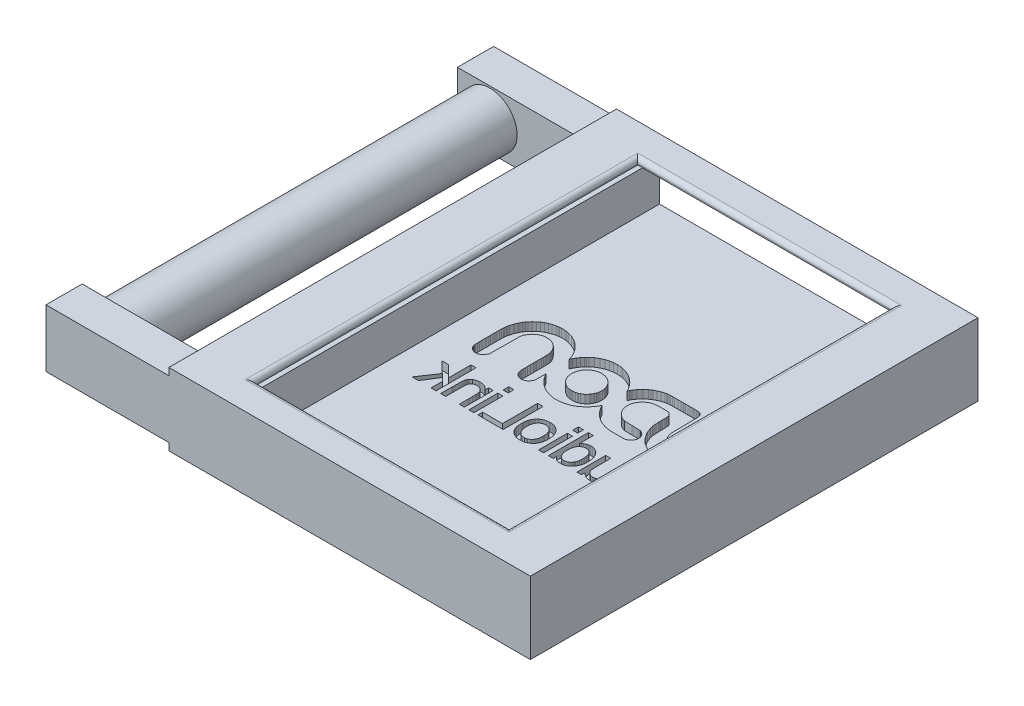
SolidWorks part; units mm, degrees
material "6061 Alloy"
ref_plane "Front" through (0, 0, 0) normal (0, 0, 1) x (1, 0, 0)
ref_plane "Top" through (0, 0, 0) normal (0, 1, 0) x (1, 0, 0)
ref_plane "Right" through (0, 0, 0) normal (1, 0, 0) x (0, 0, -1)
sketch "Sketch1" plane through (0, 0, 0) normal (0, 1, 0) x (1, 0, 0)
  line L1 (-100, -123.825) -> (100, -123.825)
  line L2 (-100, -123.825) -> (-100, 123.825)
  line L3 (-100, 123.825) -> (100, 123.825)
  line L4 (100, -123.825) -> (100, 123.825)
  line L5 (-100, -123.825) -> (100, 123.825) construction
  line L6 (-100, 123.825) -> (100, -123.825) construction
  point P0 (0, 0)
  dimension "D1" = 247.65
  dimension "D2" = 200
extrude "Boss-Extrude1" add sketch "Sketch1" along normal mid plane 40
sketch "Sketch2" plane through (0, 0, 0) normal (0, 1, 0) x (1, 0, 0)
  line L1 (-100, 123.825) -> (-168, 123.825)
  line L2 (-100, 123.825) -> (-100, 103.825)
  line L3 (-100, 103.825) -> (-168, 103.825)
  line L4 (-168, 123.825) -> (-168, 103.825)
  dimension "D1" = 68
  dimension "D2" = 20
extrude "Boss-Extrude2" add sketch "Sketch2" along normal mid plane 32
sketch "Sketch3" plane through (0, 0, 0) normal (0, 0, 1) x (1, 0, 0)
  circle A0 centre (-150, 0) radius 15
  dimension "D1" = 30
  dimension "D2" = 150
extrude "Boss-Extrude3" add sketch "Sketch3" against normal up to surface (103.825 mm away) up to face at (-134, 0, -103.825)
mirror "Mirror1" about plane through (0, 0, 0) normal (0, 0, 1) of "Boss-Extrude2", "Boss-Extrude3"
sketch "Sketch4" plane through (0, 20, 0) normal (0, 1, 0) x (1, 0, 0)
  line L1 (-70.485, -106.045) -> (70.485, -106.045)
  line L2 (-70.485, -106.045) -> (-70.485, 106.045)
  line L3 (-70.485, 106.045) -> (70.485, 106.045)
  line L4 (70.485, -106.045) -> (70.485, 106.045)
  line L5 (-70.485, -106.045) -> (70.485, 106.045) construction
  line L6 (-70.485, 106.045) -> (70.485, -106.045) construction
  point P0 (0, 0)
  dimension "D1" = 212.09
  dimension "D2" = 140.97
extrude "Cut-Extrude1" cut sketch "Sketch4" against normal blind 6.35
sketch "Sketch5" plane through (0, 0, 123.825) normal (0, 0, 1) x (1, 0, 0)
  line L0 (70.485, 13.65) -> (70.485, 20) construction
  line L1 (-87.249, 16.825) -> (87.249, 16.825)
  line L2 (-87.249, 16.825) -> (-87.249, 8.443)
  line L3 (-87.249, 8.443) -> (87.249, 8.443)
  line L4 (87.249, 16.825) -> (87.249, 8.443)
  line L5 (-87.249, 16.825) -> (87.249, 8.443) construction
  line L6 (-87.249, 8.443) -> (87.249, 16.825) construction
  line L7 (-70.485, 13.65) -> (-70.485, 20) construction
  line L8 (70.485, 13.65) -> (70.485, 20) construction
  line L9 (-70.485, 13.65) -> (-70.485, 20) construction
  line L10 (-100, 20) -> (100, 20) construction
  point P0 (0, 12.634)
  dimension "D1" = 8.382
  dimension "D2" = 3.175
  dimension "D3" = 16.764
  dimension "D4" = 16.764
extrude "Cut-Extrude2" cut sketch "Sketch5" along normal offset from surface (246.634 mm away) 16.764 from surface up to face at (0, 16.825, 106.045) offset beyond the face yes starting at face at (-67, 0, -123.825)
fillet "Fillet1" radius 2.54 4 edges at (0, 20, 106.045) (70.485, 20, 0) (-70.485, 20, 0) (0, 20, -106.045)
sketch "Sketch6" plane through (0, 0, -123.825) normal (0, 0, -1) x (-1, 0, 0)
  line L0 (87.249, 8.443) -> (-87.249, 8.443) construction
  line L1 (-76.2, -13.65) -> (76.2, -13.65)
  line L2 (-76.2, -13.65) -> (-76.2, 8.443)
  line L3 (-76.2, 8.443) -> (76.2, 8.443)
  line L4 (76.2, -13.65) -> (76.2, 8.443)
  line L5 (-76.2, -13.65) -> (76.2, 8.443) construction
  line L6 (-76.2, 8.443) -> (76.2, -13.65) construction
  line L7 (-100, -20) -> (100, -20) construction
  point P0 (0, -2.6035)
  dimension "D1" = 152.4
  dimension "D2" = 6.35
extrude "Cut-Extrude3" cut sketch "Sketch6" against normal up to surface (246.634 mm away) up to face at (0, 12.634, 122.809)
sketch "Sketch9" plane through (0, -20, 0) normal (0, -1, 0) x (1, 0, 0)
  line L0 (47.93, -1.8124) -> (48.8593, -2.019)
  line L1 (48.8593, -2.019) -> (50.5205, -2.4998)
  line L2 (50.5205, -2.4998) -> (52.0185, -3.112)
  line L3 (52.0185, -3.112) -> (53.4733, -3.9044)
  line L4 (53.4733, -3.9044) -> (54.222, -4.3835)
  line L5 (54.222, -4.3835) -> (54.8334, -4.8153)
  line L6 (54.8334, -4.8153) -> (56.0096, -5.784)
  line L7 (56.0096, -5.784) -> (57.1117, -6.8762)
  line L8 (57.1117, -6.8762) -> (58.1253, -8.0714)
  line L9 (58.1253, -8.0714) -> (59.0359, -9.3494)
  line L10 (59.0359, -9.3494) -> (59.829, -10.6898)
  line L11 (59.829, -10.6898) -> (60.49, -12.0723)
  line L12 (60.49, -12.0723) -> (61.0045, -13.4765)
  line L13 (61.0045, -13.4765) -> (61.2023, -14.1804)
  line L14 (61.2023, -14.1804) -> (61.4, -15.0085)
  line L15 (61.4, -15.0085) -> (61.6145, -16.1928)
  line L16 (61.6145, -16.1928) -> (61.7109, -17.0783)
  line L17 (61.7109, -17.0783) -> (61.7768, -18.1482)
  line L18 (61.7768, -18.1482) -> (61.8178, -19.4948)
  line L19 (61.8178, -19.4948) -> (61.8396, -21.2101)
  line L20 (61.8396, -21.2101) -> (61.8467, -22.7941)
  line L21 (61.8467, -22.7941) -> (61.8484, -24.0134)
  line L22 (61.8484, -24.0134) -> (61.8486, -24.6763)
  line L23 (61.8486, -24.6763) -> (61.8486, -25.2604)
  line L24 (61.8486, -25.2604) -> (61.8482, -26.327)
  line L25 (61.8482, -26.327) -> (61.846, -27.691)
  line L26 (61.846, -27.691) -> (61.8385, -29.1187)
  line L27 (61.8385, -29.1187) -> (61.8233, -30.1692)
  line L28 (61.8233, -30.1692) -> (61.798, -30.9181)
  line L29 (61.798, -30.9181) -> (61.7599, -31.4412)
  line L30 (61.7599, -31.4412) -> (61.6732, -31.9679)
  line L31 (61.6732, -31.9679) -> (61.5921, -32.2575)
  line L32 (61.5921, -32.2575) -> (61.4441, -32.651)
  line L33 (61.4441, -32.651) -> (61.0089, -33.4052)
  line L34 (61.0089, -33.4052) -> (60.4202, -34.0791)
  line L35 (60.4202, -34.0791) -> (59.7166, -34.6283)
  line L36 (59.7166, -34.6283) -> (59.3337, -34.8425)
  line L37 (59.3337, -34.8425) -> (58.9346, -35.0064)
  line L38 (58.9346, -35.0064) -> (58.0614, -35.1964)
  line L39 (58.0614, -35.1964) -> (57.1488, -35.2022)
  line L40 (57.1488, -35.2022) -> (56.2694, -35.0232)
  line L41 (56.2694, -35.0232) -> (55.8648, -34.8643)
  line L42 (55.8648, -34.8643) -> (55.3692, -34.5995)
  line L43 (55.3692, -34.5995) -> (54.5302, -33.9483)
  line L44 (54.5302, -33.9483) -> (53.8984, -33.1408)
  line L45 (53.8984, -33.1408) -> (53.4792, -32.1837)
  line L46 (53.4792, -32.1837) -> (53.351, -31.6514)
  line L47 (53.351, -31.6514) -> (53.3349, -31.5347)
  line L48 (53.3349, -31.5347) -> (53.3054, -31.1451)
  line L49 (53.3054, -31.1451) -> (53.2796, -30.5535)
  line L50 (53.2796, -30.5535) -> (53.2577, -29.7676)
  line L51 (53.2577, -29.7676) -> (53.2397, -28.795)
  line L52 (53.2397, -28.795) -> (53.2258, -27.6434)
  line L53 (53.2258, -27.6434) -> (53.2161, -26.3204)
  line L54 (53.2161, -26.3204) -> (53.2108, -24.8337)
  line L55 (53.2108, -24.8337) -> (53.2099, -24.0314)
  line L56 (53.2099, -24.0314) -> (53.2069, -22.5476)
  line L57 (53.2069, -22.5476) -> (53.1942, -20.5567)
  line L58 (53.1942, -20.5567) -> (53.1807, -19.4123)
  line L59 (53.1807, -19.4123) -> (53.1636, -18.4351)
  line L60 (53.1636, -18.4351) -> (53.1432, -17.6434)
  line L61 (53.1432, -17.6434) -> (53.1198, -17.055)
  line L62 (53.1198, -17.055) -> (53.0937, -16.6882)
  line L63 (53.0937, -16.6882) -> (53.0797, -16.5934)
  line L64 (53.0797, -16.5934) -> (52.8926, -15.8966)
  line L65 (52.8926, -15.8966) -> (52.3521, -14.5891)
  line L66 (52.3521, -14.5891) -> (51.6095, -13.4123)
  line L67 (51.6095, -13.4123) -> (50.6885, -12.385)
  line L68 (50.6885, -12.385) -> (49.6127, -11.5261)
  line L69 (49.6127, -11.5261) -> (48.4057, -10.8544)
  line L70 (48.4057, -10.8544) -> (47.0912, -10.3889)
  line L71 (47.0912, -10.3889) -> (45.6927, -10.1483)
  line L72 (45.6927, -10.1483) -> (44.9694, -10.1183)
  line L73 (44.9694, -10.1183) -> (43.9951, -10.1684)
  line L74 (43.9951, -10.1684) -> (42.185, -10.5837)
  line L75 (42.185, -10.5837) -> (41.2769, -10.9654)
  line L76 (41.2769, -10.9654) -> (40.8053, -11.229)
  line L77 (40.8053, -11.229) -> (39.795, -11.9878)
  line L78 (39.795, -11.9878) -> (38.8185, -12.936)
  line L79 (38.8185, -12.936) -> (38.0234, -13.93)
  line L80 (38.0234, -13.93) -> (37.7401, -14.3995)
  line L81 (37.7401, -14.3995) -> (37.5607, -14.7386)
  line L82 (37.5607, -14.7386) -> (37.2712, -15.3057)
  line L83 (37.2712, -15.3057) -> (37.0622, -15.844)
  line L84 (37.0622, -15.844) -> (36.9192, -16.4977)
  line L85 (36.9192, -16.4977) -> (36.8279, -17.4103)
  line L86 (36.8279, -17.4103) -> (36.7846, -18.3514)
  line L87 (36.7846, -18.3514) -> (36.7643, -19.1346)
  line L88 (36.7643, -19.1346) -> (36.7489, -20.0635)
  line L89 (36.7489, -20.0635) -> (36.7365, -21.1561)
  line L90 (36.7365, -21.1561) -> (36.7253, -22.4303)
  line L91 (36.7253, -22.4303) -> (36.7135, -23.9041)
  line L92 (36.7135, -23.9041) -> (36.7068, -24.7214)
  line L93 (36.7068, -24.7214) -> (36.7002, -25.5284)
  line L94 (36.7002, -25.5284) -> (36.6881, -26.9863)
  line L95 (36.6881, -26.9863) -> (36.6766, -28.2491)
  line L96 (36.6766, -28.2491) -> (36.664, -29.3326)
  line L97 (36.664, -29.3326) -> (36.6488, -30.2526)
  line L98 (36.6488, -30.2526) -> (36.6297, -31.0248)
  line L99 (36.6297, -31.0248) -> (36.5902, -31.9403)
  line L100 (36.5902, -31.9403) -> (36.5095, -32.7906)
  line L101 (36.5095, -32.7906) -> (36.3858, -33.3329)
  line L102 (36.3858, -33.3329) -> (36.0936, -33.8445)
  line L103 (36.0936, -33.8445) -> (35.8102, -34.1679)
  line L104 (35.8102, -34.1679) -> (35.3632, -34.5848)
  line L105 (35.3632, -34.5848) -> (34.8735, -34.9207)
  line L106 (34.8735, -34.9207) -> (34.6857, -35.0125)
  line L107 (34.6857, -35.0125) -> (34.2701, -35.1085)
  line L108 (34.2701, -35.1085) -> (33.7539, -35.1494)
  line L109 (33.7539, -35.1494) -> (32.9267, -35.1756)
  line L110 (32.9267, -35.1756) -> (32.0403, -35.1876)
  line L111 (32.0403, -35.1876) -> (31.2987, -35.1927)
  line L112 (31.2987, -35.1927) -> (30.4215, -35.196)
  line L113 (30.4215, -35.196) -> (29.3959, -35.1979)
  line L114 (29.3959, -35.1979) -> (28.2091, -35.1987)
  line L115 (28.2091, -35.1987) -> (26.8482, -35.1989)
  line L116 (26.8482, -35.1989) -> (26.0985, -35.1989)
  line L117 (26.0985, -35.1989) -> (25.4237, -35.1989)
  line L118 (25.4237, -35.1989) -> (24.1823, -35.1982)
  line L119 (24.1823, -35.1982) -> (22.573, -35.1954)
  line L120 (22.573, -35.1954) -> (20.8496, -35.1874)
  line L121 (20.8496, -35.1874) -> (19.5398, -35.1726)
  line L122 (19.5398, -35.1726) -> (18.5682, -35.1492)
  line L123 (18.5682, -35.1492) -> (17.8592, -35.1155)
  line L124 (17.8592, -35.1155) -> (17.1232, -35.0417)
  line L125 (17.1232, -35.0417) -> (16.7409, -34.9742)
  line L126 (16.7409, -34.9742) -> (15.8881, -34.7797)
  line L127 (15.8881, -34.7797) -> (14.2327, -34.2776)
  line L128 (14.2327, -34.2776) -> (12.6521, -33.628)
  line L129 (12.6521, -33.628) -> (11.1562, -32.8348)
  line L130 (11.1562, -32.8348) -> (10.443, -32.3856)
  line L131 (10.443, -32.3856) -> (9.6232, -31.7926)
  line L132 (9.6232, -31.7926) -> (8.0064, -30.3585)
  line L133 (8.0064, -30.3585) -> (6.5288, -28.7146)
  line L134 (6.5288, -28.7146) -> (5.3208, -27.006)
  line L135 (5.3208, -27.006) -> (4.8587, -26.1729)
  line L136 (4.8587, -26.1729) -> (4.4117, -25.2748)
  line L137 (4.4117, -25.2748) -> (3.998, -26.0686)
  line L138 (3.998, -26.0686) -> (3.5333, -26.9017)
  line L139 (3.5333, -26.9017) -> (2.4731, -28.475)
  line L140 (2.4731, -28.475) -> (1.2523, -29.914)
  line L141 (1.2523, -29.914) -> (-0.1132, -31.2064)
  line L142 (-0.1132, -31.2064) -> (-1.607, -32.34)
  line L143 (-1.607, -32.34) -> (-3.2132, -33.3026)
  line L144 (-3.2132, -33.3026) -> (-4.9154, -34.0818)
  line L145 (-4.9154, -34.0818) -> (-6.6976, -34.6655)
  line L146 (-6.6976, -34.6655) -> (-7.6137, -34.8801)
  line L147 (-7.6137, -34.8801) -> (-8.6686, -35.0616)
  line L148 (-8.6686, -35.0616) -> (-10.7713, -35.2252)
  line L149 (-10.7713, -35.2252) -> (-12.8491, -35.1279)
  line L150 (-12.8491, -35.1279) -> (-14.8833, -34.7755)
  line L151 (-14.8833, -34.7755) -> (-16.8553, -34.1736)
  line L152 (-16.8553, -34.1736) -> (-18.7463, -33.3279)
  line L153 (-18.7463, -33.3279) -> (-20.5378, -32.2442)
  line L154 (-20.5378, -32.2442) -> (-22.2109, -30.9281)
  line L155 (-22.2109, -30.9281) -> (-22.9973, -30.1847)
  line L156 (-22.9973, -30.1847) -> (-23.5248, -29.6247)
  line L157 (-23.5248, -29.6247) -> (-24.5397, -28.3737)
  line L158 (-24.5397, -28.3737) -> (-25.4499, -27.0237)
  line L159 (-25.4499, -27.0237) -> (-26.1944, -25.6654)
  line L160 (-26.1944, -25.6654) -> (-26.4854, -25.0115)
  line L161 (-26.4854, -25.0115) -> (-26.7632, -24.328)
  line L162 (-26.7632, -24.328) -> (-27.0924, -25.382)
  line L163 (-27.0924, -25.382) -> (-27.4778, -26.465)
  line L164 (-27.4778, -26.465) -> (-28.506, -28.5948)
  line L165 (-28.506, -28.5948) -> (-29.8176, -30.5858)
  line L166 (-29.8176, -30.5858) -> (-31.3414, -32.3296)
  line L167 (-31.3414, -32.3296) -> (-32.1605, -33.075)
  line L168 (-32.1605, -33.075) -> (-33.1539, -33.8619)
  line L169 (-33.1539, -33.8619) -> (-35.1274, -35.1509)
  line L170 (-35.1274, -35.1509) -> (-37.1834, -36.1065)
  line L171 (-37.1834, -36.1065) -> (-39.442, -36.7846)
  line L172 (-39.442, -36.7846) -> (-40.6848, -37.0371)
  line L173 (-40.6848, -37.0371) -> (-41.3523, -37.1437)
  line L174 (-41.3523, -37.1437) -> (-42.5862, -37.2657)
  line L175 (-42.5862, -37.2657) -> (-43.7685, -37.2661)
  line L176 (-43.7685, -37.2661) -> (-44.9993, -37.1451)
  line L177 (-44.9993, -37.1451) -> (-45.6641, -37.0391)
  line L178 (-45.6641, -37.0391) -> (-46.5297, -36.868)
  line L179 (-46.5297, -36.868) -> (-48.1852, -36.4278)
  line L180 (-48.1852, -36.4278) -> (-49.7428, -35.8549)
  line L181 (-49.7428, -35.8549) -> (-51.2063, -35.1471)
  line L182 (-51.2063, -35.1471) -> (-52.5794, -34.302)
  line L183 (-52.5794, -34.302) -> (-53.8658, -33.3174)
  line L184 (-53.8658, -33.3174) -> (-55.0694, -32.1909)
  line L185 (-55.0694, -32.1909) -> (-56.1937, -30.9202)
  line L186 (-56.1937, -30.9202) -> (-56.7274, -30.2301)
  line L187 (-56.7274, -30.2301) -> (-57.2616, -29.4642)
  line L188 (-57.2616, -29.4642) -> (-58.1905, -27.8525)
  line L189 (-58.1905, -27.8525) -> (-58.9425, -26.1127)
  line L190 (-58.9425, -26.1127) -> (-59.5287, -24.2193)
  line L191 (-59.5287, -24.2193) -> (-59.7631, -23.2069)
  line L192 (-59.7631, -23.2069) -> (-59.8639, -22.7055)
  line L193 (-59.8639, -22.7055) -> (-59.9693, -21.9562)
  line L194 (-59.9693, -21.9562) -> (-60.0143, -21.2913)
  line L195 (-60.0143, -21.2913) -> (-60.0433, -20.3602)
  line L196 (-60.0433, -20.3602) -> (-60.0598, -19.0481)
  line L197 (-60.0598, -19.0481) -> (-60.0662, -17.7451)
  line L198 (-60.0662, -17.7451) -> (-60.0684, -16.6976)
  line L199 (-60.0684, -16.6976) -> (-60.0695, -15.4904)
  line L200 (-60.0695, -15.4904) -> (-60.0699, -14.109)
  line L201 (-60.0699, -14.109) -> (-60.07, -13.3486)
  line L202 (-60.07, -13.3486) -> (-60.0679, -11.6508)
  line L203 (-60.0679, -11.6508) -> (-60.057, -9.3283)
  line L204 (-60.057, -9.3283) -> (-60.0452, -7.9785)
  line L205 (-60.0452, -7.9785) -> (-60.0302, -6.8266)
  line L206 (-60.0302, -6.8266) -> (-60.0125, -5.9063)
  line L207 (-60.0125, -5.9063) -> (-59.9926, -5.2512)
  line L208 (-59.9926, -5.2512) -> (-59.9708, -4.8951)
  line L209 (-59.9708, -4.8951) -> (-59.9593, -4.8396)
  line L210 (-59.9593, -4.8396) -> (-59.9043, -4.756)
  line L211 (-59.9043, -4.756) -> (-59.7656, -4.4437)
  line L212 (-59.7656, -4.4437) -> (-59.699, -4.2534)
  line L213 (-59.699, -4.2534) -> (-59.6021, -4.0237)
  line L214 (-59.6021, -4.0237) -> (-59.2623, -3.4944)
  line L215 (-59.2623, -3.4944) -> (-58.5336, -2.6951)
  line L216 (-58.5336, -2.6951) -> (-58.0151, -2.2908)
  line L217 (-58.0151, -2.2908) -> (-57.7273, -2.1311)
  line L218 (-57.7273, -2.1311) -> (-57.055, -1.8689)
  line L219 (-57.055, -1.8689) -> (-56.3263, -1.7002)
  line L220 (-56.3263, -1.7002) -> (-55.6278, -1.6448)
  line L221 (-55.6278, -1.6448) -> (-55.3171, -1.666)
  line L222 (-55.3171, -1.666) -> (-54.7785, -1.7767)
  line L223 (-54.7785, -1.7767) -> (-53.7585, -2.2139)
  line L224 (-53.7585, -2.2139) -> (-52.8596, -2.9046)
  line L225 (-52.8596, -2.9046) -> (-52.136, -3.807)
  line L226 (-52.136, -3.807) -> (-51.8568, -4.3246)
  line L227 (-51.8568, -4.3246) -> (-51.4985, -5.0999)
  line L228 (-51.4985, -5.0999) -> (-51.4312, -13.6724)
  line L229 (-51.4312, -13.6724) -> (-51.4252, -14.4369)
  line L230 (-51.4252, -14.4369) -> (-51.4139, -15.8277)
  line L231 (-51.4139, -15.8277) -> (-51.4034, -17.0448)
  line L232 (-51.4034, -17.0448) -> (-51.393, -18.101)
  line L233 (-51.393, -18.101) -> (-51.3824, -19.0094)
  line L234 (-51.3824, -19.0094) -> (-51.371, -19.7826)
  line L235 (-51.371, -19.7826) -> (-51.3516, -20.7173)
  line L236 (-51.3516, -20.7173) -> (-51.3186, -21.6106)
  line L237 (-51.3186, -21.6106) -> (-51.2741, -22.1949)
  line L238 (-51.2741, -22.1949) -> (-51.1775, -22.7169)
  line L239 (-51.1775, -22.7169) -> (-51.0877, -22.9784)
  line L240 (-51.0877, -22.9784) -> (-50.776, -23.7156)
  line L241 (-50.776, -23.7156) -> (-49.9983, -25.0764)
  line L242 (-49.9983, -25.0764) -> (-49.0459, -26.2477)
  line L243 (-49.0459, -26.2477) -> (-47.9559, -27.1837)
  line L244 (-47.9559, -27.1837) -> (-47.371, -27.5492)
  line L245 (-47.371, -27.5492) -> (-46.8306, -27.8335)
  line L246 (-46.8306, -27.8335) -> (-45.853, -28.2463)
  line L247 (-45.853, -28.2463) -> (-44.8852, -28.4825)
  line L248 (-44.8852, -28.4825) -> (-43.7739, -28.5794)
  line L249 (-43.7739, -28.5794) -> (-43.1165, -28.5874)
  line L250 (-43.1165, -28.5874) -> (-42.6016, -28.5831)
  line L251 (-42.6016, -28.5831) -> (-41.8473, -28.5534)
  line L252 (-41.8473, -28.5534) -> (-41.2968, -28.4714)
  line L253 (-41.2968, -28.4714) -> (-40.7543, -28.3077)
  line L254 (-40.7543, -28.3077) -> (-40.4247, -28.186)
  line L255 (-40.4247, -28.186) -> (-39.9657, -27.9967)
  line L256 (-39.9657, -27.9967) -> (-39.0406, -27.5409)
  line L257 (-39.0406, -27.5409) -> (-38.6885, -27.3306)
  line L258 (-38.6885, -27.3306) -> (-38.2703, -27.0276)
  line L259 (-38.2703, -27.0276) -> (-37.4493, -26.2898)
  line L260 (-37.4493, -26.2898) -> (-36.6972, -25.4315)
  line L261 (-36.6972, -25.4315) -> (-36.0723, -24.5191)
  line L262 (-36.0723, -24.5191) -> (-35.8257, -24.0634)
  line L263 (-35.8257, -24.0634) -> (-35.5228, -23.4356)
  line L264 (-35.5228, -23.4356) -> (-35.2091, -22.5816)
  line L265 (-35.2091, -22.5816) -> (-35.0772, -21.8826)
  line L266 (-35.0772, -21.8826) -> (-34.9942, -20.9297)
  line L267 (-34.9942, -20.9297) -> (-34.9571, -19.9706)
  line L268 (-34.9571, -19.9706) -> (-34.9417, -19.1848)
  line L269 (-34.9417, -19.1848) -> (-34.9322, -18.2629)
  line L270 (-34.9322, -18.2629) -> (-34.9272, -17.1889)
  line L271 (-34.9272, -17.1889) -> (-34.9253, -15.9467)
  line L272 (-34.9253, -15.9467) -> (-34.925, -14.52)
  line L273 (-34.925, -14.52) -> (-34.925, -13.7326)
  line L274 (-34.925, -13.7326) -> (-34.9244, -12.8119)
  line L275 (-34.9244, -12.8119) -> (-34.9199, -11.1176)
  line L276 (-34.9199, -11.1176) -> (-34.911, -9.6236)
  line L277 (-34.911, -9.6236) -> (-34.8978, -8.335)
  line L278 (-34.8978, -8.335) -> (-34.8803, -7.2571)
  line L279 (-34.8803, -7.2571) -> (-34.8587, -6.3951)
  line L280 (-34.8587, -6.3951) -> (-34.833, -5.7541)
  line L281 (-34.833, -5.7541) -> (-34.8033, -5.3394)
  line L282 (-34.8033, -5.3394) -> (-34.787, -5.2185)
  line L283 (-34.787, -5.2185) -> (-34.6999, -4.8323)
  line L284 (-34.6999, -4.8323) -> (-34.4399, -4.1124)
  line L285 (-34.4399, -4.1124) -> (-34.0739, -3.4695)
  line L286 (-34.0739, -3.4695) -> (-33.6116, -2.9118)
  line L287 (-33.6116, -2.9118) -> (-33.063, -2.4477)
  line L288 (-33.063, -2.4477) -> (-32.4378, -2.0856)
  line L289 (-32.4378, -2.0856) -> (-31.746, -1.8338)
  line L290 (-31.746, -1.8338) -> (-30.9973, -1.7005)
  line L291 (-30.9973, -1.7005) -> (-30.6047, -1.681)
  line L292 (-30.6047, -1.681) -> (-29.981, -1.7185)
  line L293 (-29.981, -1.7185) -> (-28.8386, -2.046)
  line L294 (-28.8386, -2.046) -> (-27.851, -2.7004)
  line L295 (-27.851, -2.7004) -> (-27.0358, -3.6702)
  line L296 (-27.0358, -3.6702) -> (-26.6984, -4.2697)
  line L297 (-26.6984, -4.2697) -> (-26.585, -4.5073)
  line L298 (-26.585, -4.5073) -> (-26.4362, -4.9681)
  line L299 (-26.4362, -4.9681) -> (-26.3751, -5.4722)
  line L300 (-26.3751, -5.4722) -> (-26.3502, -5.9652)
  line L301 (-26.3502, -5.9652) -> (-26.3328, -6.6345)
  line L302 (-26.3328, -6.6345) -> (-26.3184, -7.5234)
  line L303 (-26.3184, -7.5234) -> (-26.3109, -8.0637)
  line L304 (-26.3109, -8.0637) -> (-26.2689, -11.1546)
  line L305 (-26.2689, -11.1546) -> (-25.7104, -10.1744)
  line L306 (-25.7104, -10.1744) -> (-25.2365, -9.3917)
  line L307 (-25.2365, -9.3917) -> (-24.177, -7.917)
  line L308 (-24.177, -7.917) -> (-22.9796, -6.5718)
  line L309 (-22.9796, -6.5718) -> (-21.6581, -5.3662)
  line L310 (-21.6581, -5.3662) -> (-20.2262, -4.3101)
  line L311 (-20.2262, -4.3101) -> (-18.6974, -3.4138)
  line L312 (-18.6974, -3.4138) -> (-17.0854, -2.6873)
  line L313 (-17.0854, -2.6873) -> (-15.404, -2.1406)
  line L314 (-15.404, -2.1406) -> (-14.5415, -1.9379)
  line L315 (-14.5415, -1.9379) -> (-14.0986, -1.847)
  line L316 (-14.0986, -1.847) -> (-13.2307, -1.6695)
  line L317 (-13.2307, -1.6695) -> (-12.9126, -1.6047)
  line L318 (-12.9126, -1.6047) -> (-12.466, -1.5337)
  line L319 (-12.466, -1.5337) -> (-11.4389, -1.475)
  line L320 (-11.4389, -1.475) -> (-9.655, -1.5789)
  line L321 (-9.655, -1.5789) -> (-7.0806, -2.0304)
  line L322 (-7.0806, -2.0304) -> (-5.2179, -2.5662)
  line L323 (-5.2179, -2.5662) -> (-4.1006, -3.001)
  line L324 (-4.1006, -3.001) -> (-3.5977, -3.2385)
  line L325 (-3.5977, -3.2385) -> (-2.4454, -3.8854)
  line L326 (-2.4454, -3.8854) -> (-0.2515, -5.484)
  line L327 (-0.2515, -5.484) -> (1.7045, -7.4005)
  line L328 (1.7045, -7.4005) -> (3.3142, -9.5288)
  line L329 (3.3142, -9.5288) -> (3.9552, -10.6392)
  line L330 (3.9552, -10.6392) -> (4.3904, -11.4794)
  line L331 (4.3904, -11.4794) -> (4.9413, -10.4279)
  line L332 (4.9413, -10.4279) -> (5.3263, -9.7401)
  line L333 (5.3263, -9.7401) -> (6.2161, -8.4126)
  line L334 (6.2161, -8.4126) -> (7.2502, -7.1614)
  line L335 (7.2502, -7.1614) -> (8.4106, -6.0016)
  line L336 (8.4106, -6.0016) -> (9.6792, -4.9484)
  line L337 (9.6792, -4.9484) -> (11.0377, -4.0168)
  line L338 (11.0377, -4.0168) -> (12.468, -3.2219)
  line L339 (12.468, -3.2219) -> (13.9519, -2.5787)
  line L340 (13.9519, -2.5787) -> (14.7084, -2.3187)
  line L341 (14.7084, -2.3187) -> (15.5331, -2.0749)
  line L342 (15.5331, -2.0749) -> (17.1024, -1.7339)
  line L343 (17.1024, -1.7339) -> (18.4035, -1.5869)
  line L344 (18.4035, -1.5869) -> (19.4225, -1.5316)
  line L345 (19.4225, -1.5316) -> (20.6203, -1.5047)
  line L346 (20.6203, -1.5047) -> (22.0461, -1.5013)
  line L347 (22.0461, -1.5013) -> (22.86, -1.5068)
  line L348 (22.86, -1.5068) -> (26.9875, -1.5439)
  line L349 (26.9875, -1.5439) -> (27.7793, -1.9096)
  line L350 (27.7793, -1.9096) -> (28.2315, -2.1493)
  line L351 (28.2315, -2.1493) -> (29.0123, -2.7454)
  line L352 (29.0123, -2.7454) -> (29.621, -3.4699)
  line L353 (29.621, -3.4699) -> (30.0487, -4.2897)
  line L354 (30.0487, -4.2897) -> (30.2865, -5.172)
  line L355 (30.2865, -5.172) -> (30.3255, -6.0836)
  line L356 (30.3255, -6.0836) -> (30.1568, -6.9916)
  line L357 (30.1568, -6.9916) -> (29.7716, -7.8632)
  line L358 (29.7716, -7.8632) -> (29.495, -8.2749)
  line L359 (29.495, -8.2749) -> (29.0358, -8.7861)
  line L360 (29.0358, -8.7861) -> (27.8992, -9.6272)
  line L361 (27.8992, -9.6272) -> (27.3275, -9.8789)
  line L362 (27.3275, -9.8789) -> (27.2543, -9.8968)
  line L363 (27.2543, -9.8968) -> (27.0073, -9.9317)
  line L364 (27.0073, -9.9317) -> (26.3933, -9.981)
  line L365 (26.3933, -9.981) -> (25.1434, -10.0404)
  line L366 (25.1434, -10.0404) -> (23.4327, -10.0907)
  line L367 (23.4327, -10.0907) -> (22.4155, -10.1121)
  line L368 (22.4155, -10.1121) -> (17.9705, -10.1949)
  line L369 (17.9705, -10.1949) -> (17.0207, -10.5531)
  line L370 (17.0207, -10.5531) -> (16.3324, -10.846)
  line L371 (16.3324, -10.846) -> (15.0675, -11.5821)
  line L372 (15.0675, -11.5821) -> (13.9649, -12.4963)
  line L373 (13.9649, -12.4963) -> (13.0414, -13.5613)
  line L374 (13.0414, -13.5613) -> (12.3136, -14.7502)
  line L375 (12.3136, -14.7502) -> (11.7978, -16.0359)
  line L376 (11.7978, -16.0359) -> (11.5108, -17.3913)
  line L377 (11.5108, -17.3913) -> (11.4692, -18.7893)
  line L378 (11.4692, -18.7893) -> (11.5455, -19.4959)
  line L379 (11.5455, -19.4959) -> (11.6767, -20.1945)
  line L380 (11.6767, -20.1945) -> (12.0623, -21.4564)
  line L381 (12.0623, -21.4564) -> (12.6362, -22.5846)
  line L382 (12.6362, -22.5846) -> (13.4271, -23.6357)
  line L383 (13.4271, -23.6357) -> (13.9129, -24.1499)
  line L384 (13.9129, -24.1499) -> (14.2939, -24.5126)
  line L385 (14.2939, -24.5126) -> (15.0462, -25.1282)
  line L386 (15.0462, -25.1282) -> (16.2354, -25.8314)
  line L387 (16.2354, -25.8314) -> (17.1352, -26.1956)
  line L388 (17.1352, -26.1956) -> (17.6372, -26.3521)
  line L389 (17.6372, -26.3521) -> (18.7495, -26.5798)
  line L390 (18.7495, -26.5798) -> (20.1313, -26.7051)
  line L391 (20.1313, -26.7051) -> (21.4348, -26.7401)
  line L392 (21.4348, -26.7401) -> (22.4663, -26.7384)
  line L393 (22.4663, -26.7384) -> (23.0378, -26.7308)
  line L394 (23.0378, -26.7308) -> (23.5826, -26.7212)
  line L395 (23.5826, -26.7212) -> (24.4877, -26.6984)
  line L396 (24.4877, -26.6984) -> (25.1826, -26.6629)
  line L397 (25.1826, -26.6629) -> (25.7101, -26.6053)
  line L398 (25.7101, -26.6053) -> (26.2808, -26.4567)
  line L399 (26.2808, -26.4567) -> (26.8544, -26.0928)
  line L400 (26.8544, -26.0928) -> (27.1571, -25.8185)
  line L401 (27.1571, -25.8185) -> (27.4357, -25.5494)
  line L402 (27.4357, -25.5494) -> (27.7976, -24.9893)
  line L403 (27.7976, -24.9893) -> (27.9422, -24.292)
  line L404 (27.9422, -24.292) -> (27.9993, -23.5723)
  line L405 (27.9993, -23.5723) -> (28.0381, -22.5723)
  line L406 (28.0381, -22.5723) -> (28.0698, -21.2265)
  line L407 (28.0698, -21.2265) -> (28.0865, -20.4034)
  line L408 (28.0865, -20.4034) -> (28.0982, -19.8547)
  line L409 (28.0982, -19.8547) -> (28.1231, -18.861)
  line L410 (28.1231, -18.861) -> (28.1652, -17.6148)
  line L411 (28.1652, -17.6148) -> (28.2323, -16.3682)
  line L412 (28.2323, -16.3682) -> (28.3151, -15.5383)
  line L413 (28.3151, -15.5383) -> (28.3635, -15.2599)
  line L414 (28.3635, -15.2599) -> (28.7437, -13.783)
  line L415 (28.7437, -13.783) -> (29.837, -11.001)
  line L416 (29.837, -11.001) -> (31.3485, -8.4905)
  line L417 (31.3485, -8.4905) -> (32.7383, -6.8163)
  line L418 (32.7383, -6.8163) -> (33.7796, -5.8114)
  line L419 (33.7796, -5.8114) -> (34.3332, -5.3448)
  line L420 (34.3332, -5.3448) -> (35.1932, -4.6885)
  line L421 (35.1932, -4.6885) -> (36.9311, -3.5871)
  line L422 (36.9311, -3.5871) -> (38.7596, -2.7366)
  line L423 (38.7596, -2.7366) -> (40.7584, -2.0999)
  line L424 (40.7584, -2.0999) -> (41.8465, -1.85)
  line L425 (41.8465, -1.85) -> (42.6782, -1.6958)
  line L426 (42.6782, -1.6958) -> (44.211, -1.5159)
  line L427 (44.211, -1.5159) -> (45.6624, -1.507)
  line L428 (45.6624, -1.507) -> (47.1435, -1.6682)
  line L429 (47.1435, -1.6682) -> (47.93, -1.8124)
  line L430 (22.479, 27.6239) -> (22.8987, 27.475)
  line L431 (22.8987, 27.475) -> (23.6208, 27.1527)
  line L432 (23.6208, 27.1527) -> (24.2551, 26.7544)
  line L433 (24.2551, 26.7544) -> (24.884, 26.2286)
  line L434 (24.884, 26.2286) -> (25.2222, 25.9016)
  line L435 (25.2222, 25.9016) -> (25.5751, 25.5248)
  line L436 (25.5751, 25.5248) -> (26.1896, 24.7175)
  line L437 (26.1896, 24.7175) -> (26.6918, 23.8219)
  line L438 (26.6918, 23.8219) -> (27.0931, 22.8177)
  line L439 (27.0931, 22.8177) -> (27.2595, 22.2686)
  line L440 (27.2595, 22.2686) -> (27.3162, 22.0251)
  line L441 (27.3162, 22.0251) -> (27.407, 21.4175)
  line L442 (27.407, 21.4175) -> (27.4863, 20.2929)
  line L443 (27.4863, 20.2929) -> (27.4858, 18.6436)
  line L444 (27.4858, 18.6436) -> (27.4058, 17.5012)
  line L445 (27.4058, 17.5012) -> (27.3146, 16.8732)
  line L446 (27.3146, 16.8732) -> (27.2577, 16.6171)
  line L447 (27.2577, 16.6171) -> (27.0032, 15.7815)
  line L448 (27.0032, 15.7815) -> (26.3203, 14.2855)
  line L449 (26.3203, 14.2855) -> (25.4256, 13.0509)
  line L450 (25.4256, 13.0509) -> (24.3438, 12.1115)
  line L451 (24.3438, 12.1115) -> (23.7403, 11.7631)
  line L452 (23.7403, 11.7631) -> (23.3338, 11.5756)
  line L453 (23.3338, 11.5756) -> (22.5586, 11.3014)
  line L454 (22.5586, 11.3014) -> (21.7685, 11.1489)
  line L455 (21.7685, 11.1489) -> (20.8854, 11.1028)
  line L456 (20.8854, 11.1028) -> (20.3844, 11.115)
  line L457 (20.3844, 11.115) -> (20.0415, 11.1329)
  line L458 (20.0415, 11.1329) -> (19.5012, 11.1873)
  line L459 (19.5012, 11.1873) -> (18.8608, 11.3595)
  line L460 (18.8608, 11.3595) -> (18.396, 11.5692)
  line L461 (18.396, 11.5692) -> (17.6424, 12.0268)
  line L462 (17.6424, 12.0268) -> (16.9802, 12.5609)
  line L463 (16.9802, 12.5609) -> (16.383, 13.1497)
  line L464 (16.383, 13.1497) -> (16.383, 9.2636)
  line L465 (16.383, 9.2636) -> (16.383, 5.3776)
  line L466 (16.383, 5.3776) -> (14.986, 5.3776)
  line L467 (14.986, 5.3776) -> (13.589, 5.3776)
  line L468 (13.589, 5.3776) -> (13.589, 16.4266)
  line L469 (13.589, 16.4266) -> (13.589, 27.4756)
  line L470 (13.589, 27.4756) -> (14.9225, 27.4756)
  line L471 (14.9225, 27.4756) -> (16.256, 27.4756)
  line L472 (16.256, 27.4756) -> (16.256, 26.592)
  line L473 (16.256, 26.592) -> (16.256, 25.7085)
  line L474 (16.256, 25.7085) -> (16.8459, 26.3391)
  line L475 (16.8459, 26.3391) -> (17.1471, 26.6263)
  line L476 (17.1471, 26.6263) -> (17.8866, 27.1671)
  line L477 (17.8866, 27.1671) -> (18.2698, 27.3803)
  line L478 (18.2698, 27.3803) -> (18.7579, 27.6029)
  line L479 (18.7579, 27.6029) -> (19.4199, 27.7687)
  line L480 (19.4199, 27.7687) -> (20.0305, 27.8114)
  line L481 (20.0305, 27.8114) -> (20.4421, 27.8237)
  line L482 (20.4421, 27.8237) -> (20.8023, 27.8296)
  line L483 (20.8023, 27.8296) -> (21.3963, 27.8185)
  line L484 (21.3963, 27.8185) -> (22.0791, 27.7338)
  line L485 (22.0791, 27.7338) -> (22.479, 27.6239)
  line L486 (0.2993, 27.6553) -> (1.0056, 27.441)
  line L487 (1.0056, 27.441) -> (2.3336, 26.7855)
  line L488 (2.3336, 26.7855) -> (3.4968, 25.8685)
  line L489 (3.4968, 25.8685) -> (4.4331, 24.7391)
  line L490 (4.4331, 24.7391) -> (4.7966, 24.1101)
  line L491 (4.7966, 24.1101) -> (5.0057, 23.6647)
  line L492 (5.0057, 23.6647) -> (5.3258, 22.7767)
  line L493 (5.3258, 22.7767) -> (5.5336, 21.806)
  line L494 (5.5336, 21.806) -> (5.6512, 20.6494)
  line L495 (5.6512, 20.6494) -> (5.683, 19.9691)
  line L496 (5.683, 19.9691) -> (5.6979, 19.1586)
  line L497 (5.6979, 19.1586) -> (5.6354, 17.7727)
  line L498 (5.6354, 17.7727) -> (5.4312, 16.5926)
  line L499 (5.4312, 16.5926) -> (5.0632, 15.4892)
  line L500 (5.0632, 15.4892) -> (4.8107, 14.9259)
  line L501 (4.8107, 14.9259) -> (4.5421, 14.4178)
  line L502 (4.5421, 14.4178) -> (3.9128, 13.5164)
  line L503 (3.9128, 13.5164) -> (3.1506, 12.7581)
  line L504 (3.1506, 12.7581) -> (2.2435, 12.1308)
  line L505 (2.2435, 12.1308) -> (1.7317, 11.8626)
  line L506 (1.7317, 11.8626) -> (1.2778, 11.656)
  line L507 (1.2778, 11.656) -> (0.4519, 11.3533)
  line L508 (0.4519, 11.3533) -> (-0.3621, 11.1771)
  line L509 (-0.3621, 11.1771) -> (-1.2809, 11.102)
  line L510 (-1.2809, 11.102) -> (-1.816, 11.0944)
  line L511 (-1.816, 11.0944) -> (-2.4479, 11.1159)
  line L512 (-2.4479, 11.1159) -> (-3.6445, 11.2798)
  line L513 (-3.6445, 11.2798) -> (-4.7465, 11.6015)
  line L514 (-4.7465, 11.6015) -> (-5.7479, 12.0769)
  line L515 (-5.7479, 12.0769) -> (-6.6427, 12.7016)
  line L516 (-6.6427, 12.7016) -> (-7.4249, 13.4715)
  line L517 (-7.4249, 13.4715) -> (-8.0885, 14.3824)
  line L518 (-8.0885, 14.3824) -> (-8.6273, 15.4301)
  line L519 (-8.6273, 15.4301) -> (-8.8481, 16.0039)
  line L520 (-8.8481, 16.0039) -> (-9.0313, 16.5932)
  line L521 (-9.0313, 16.5932) -> (-9.1787, 17.5052)
  line L522 (-9.1787, 17.5052) -> (-9.2267, 18.3941)
  line L523 (-9.2267, 18.3941) -> (-9.2446, 18.9903)
  line L524 (-9.2446, 18.9903) -> (-9.2554, 19.8309)
  line L525 (-9.2554, 19.8309) -> (-9.1924, 21.2543)
  line L526 (-9.1924, 21.2543) -> (-9.0002, 22.4368)
  line L527 (-9.0002, 22.4368) -> (-8.6586, 23.5017)
  line L528 (-8.6586, 23.5017) -> (-8.4256, 24.0285)
  line L529 (-8.4256, 24.0285) -> (-8.0707, 24.6639)
  line L530 (-8.0707, 24.6639) -> (-7.1311, 25.8054)
  line L531 (-7.1311, 25.8054) -> (-5.9292, 26.7403)
  line L532 (-5.9292, 26.7403) -> (-4.5186, 27.4269)
  line L533 (-4.5186, 27.4269) -> (-3.7516, 27.6642)
  line L534 (-3.7516, 27.6642) -> (-3.3479, 27.7427)
  line L535 (-3.3479, 27.7427) -> (-2.321, 27.8312)
  line L536 (-2.321, 27.8312) -> (-1.1768, 27.8287)
  line L537 (-1.1768, 27.8287) -> (-0.1256, 27.7357)
  line L538 (-0.1256, 27.7357) -> (0.2993, 27.6553)
  line L539 (63.5569, 26.3643) -> (63.4932, 26.1997)
  line L540 (63.4932, 26.1997) -> (63.2571, 25.5875)
  line L541 (63.2571, 25.5875) -> (62.8908, 24.6356)
  line L542 (62.8908, 24.6356) -> (62.4116, 23.3892)
  line L543 (62.4116, 23.3892) -> (61.8368, 21.8934)
  line L544 (61.8368, 21.8934) -> (61.1838, 20.1935)
  line L545 (61.1838, 20.1935) -> (60.0957, 17.3597)
  line L546 (60.0957, 17.3597) -> (59.3232, 15.3471)
  line L547 (59.3232, 15.3471) -> (55.5217, 5.4411)
  line L548 (55.5217, 5.4411) -> (53.8743, 5.4057)
  line L549 (53.8743, 5.4057) -> (53.4453, 5.3985)
  line L550 (53.4453, 5.3985) -> (52.7982, 5.4018)
  line L551 (52.7982, 5.4018) -> (52.3968, 5.4316)
  line L552 (52.3968, 5.4316) -> (52.198, 5.491)
  line L553 (52.198, 5.491) -> (52.1612, 5.5327)
  line L554 (52.1612, 5.5327) -> (52.1124, 5.6527)
  line L555 (52.1124, 5.6527) -> (51.8841, 6.2124)
  line L556 (51.8841, 6.2124) -> (51.5015, 7.1497)
  line L557 (51.5015, 7.1497) -> (50.9886, 8.4057)
  line L558 (50.9886, 8.4057) -> (50.3694, 9.9219)
  line L559 (50.3694, 9.9219) -> (49.6678, 11.6395)
  line L560 (49.6678, 11.6395) -> (48.5134, 14.4652)
  line L561 (48.5134, 14.4652) -> (46.91, 18.3897)
  line L562 (46.91, 18.3897) -> (45.7641, 21.1941)
  line L563 (45.7641, 21.1941) -> (45.0721, 22.8873)
  line L564 (45.0721, 22.8873) -> (44.4657, 24.371)
  line L565 (44.4657, 24.371) -> (43.9688, 25.5865)
  line L566 (43.9688, 25.5865) -> (43.6054, 26.475)
  line L567 (43.6054, 26.475) -> (43.3995, 26.9779)
  line L568 (43.3995, 26.9779) -> (43.3632, 27.0664)
  line L569 (43.3632, 27.0664) -> (43.19, 27.4827)
  line L570 (43.19, 27.4827) -> (44.9249, 27.4474)
  line L571 (44.9249, 27.4474) -> (46.6599, 27.4121)
  line L572 (46.6599, 27.4121) -> (47.9301, 24.0768)
  line L573 (47.9301, 24.0768) -> (49.2004, 20.7415)
  line L574 (49.2004, 20.7415) -> (53.7784, 20.7748)
  line L575 (53.7784, 20.7748) -> (58.3565, 20.8081)
  line L576 (58.3565, 20.8081) -> (59.563, 24.1414)
  line L577 (59.563, 24.1414) -> (60.7695, 27.4747)
  line L578 (60.7695, 27.4747) -> (62.3793, 27.4752)
  line L579 (62.3793, 27.4752) -> (63.9891, 27.4756)
  line L580 (63.9891, 27.4756) -> (63.5569, 26.3643)
  line L581 (-48.514, 16.4266) -> (-48.514, 5.3776)
  line L582 (-48.514, 5.3776) -> (-49.911, 5.3776)
  line L583 (-49.911, 5.3776) -> (-51.308, 5.3776)
  line L584 (-51.308, 5.3776) -> (-51.308, 11.6192)
  line L585 (-51.308, 11.6192) -> (-51.308, 17.8608)
  line L586 (-51.308, 17.8608) -> (-54.4314, 14.6672)
  line L587 (-54.4314, 14.6672) -> (-57.5549, 11.4736)
  line L588 (-57.5549, 11.4736) -> (-59.4162, 11.4765)
  line L589 (-59.4162, 11.4765) -> (-61.2775, 11.4795)
  line L590 (-61.2775, 11.4795) -> (-60.6425, 12.0714)
  line L591 (-60.6425, 12.0714) -> (-60.4652, 12.2392)
  line L592 (-60.4652, 12.2392) -> (-59.8707, 12.8119)
  line L593 (-59.8707, 12.8119) -> (-58.5678, 14.0804)
  line L594 (-58.5678, 14.0804) -> (-57.5721, 15.0561)
  line L595 (-57.5721, 15.0561) -> (-55.1367, 17.4489)
  line L596 (-55.1367, 17.4489) -> (-58.4992, 22.4622)
  line L597 (-58.4992, 22.4622) -> (-61.8616, 27.4756)
  line L598 (-61.8616, 27.4756) -> (-60.1091, 27.4712)
  line L599 (-60.1091, 27.4712) -> (-58.3565, 27.4668)
  line L600 (-58.3565, 27.4668) -> (-55.753, 23.4139)
  line L601 (-55.753, 23.4139) -> (-53.1495, 19.3611)
  line L602 (-53.1495, 19.3611) -> (-52.2288, 20.2719)
  line L603 (-52.2288, 20.2719) -> (-51.308, 21.1827)
  line L604 (-51.308, 21.1827) -> (-51.308, 24.3291)
  line L605 (-51.308, 24.3291) -> (-51.308, 27.4756)
  line L606 (-51.308, 27.4756) -> (-49.911, 27.4756)
  line L607 (-49.911, 27.4756) -> (-48.514, 27.4756)
  line L608 (-48.514, 27.4756) -> (-48.514, 16.4266)
  line L609 (-32.893, 19.4746) -> (-32.893, 11.4736)
  line L610 (-32.893, 11.4736) -> (-34.163, 11.4736)
  line L611 (-34.163, 11.4736) -> (-35.433, 11.4736)
  line L612 (-35.433, 11.4736) -> (-35.433, 12.4454)
  line L613 (-35.433, 12.4454) -> (-35.433, 13.4172)
  line L614 (-35.433, 13.4172) -> (-36.1689, 12.7153)
  line L615 (-36.1689, 12.7153) -> (-36.6616, 12.2805)
  line L616 (-36.6616, 12.2805) -> (-37.6571, 11.6332)
  line L617 (-37.6571, 11.6332) -> (-38.7441, 11.255)
  line L618 (-38.7441, 11.255) -> (-40.0161, 11.1136)
  line L619 (-40.0161, 11.1136) -> (-40.7508, 11.1214)
  line L620 (-40.7508, 11.1214) -> (-41.4958, 11.1796)
  line L621 (-41.4958, 11.1796) -> (-42.7889, 11.4567)
  line L622 (-42.7889, 11.4567) -> (-43.8449, 11.9604)
  line L623 (-43.8449, 11.9604) -> (-44.6948, 12.7055)
  line L624 (-44.6948, 12.7055) -> (-45.0521, 13.1731)
  line L625 (-45.0521, 13.1731) -> (-45.3274, 13.5967)
  line L626 (-45.3274, 13.5967) -> (-45.6172, 14.2253)
  line L627 (-45.6172, 14.2253) -> (-45.7432, 14.777)
  line L628 (-45.7432, 14.777) -> (-45.8275, 15.5443)
  line L629 (-45.8275, 15.5443) -> (-45.8805, 16.6212)
  line L630 (-45.8805, 16.6212) -> (-45.9125, 18.1016)
  line L631 (-45.9125, 18.1016) -> (-45.9289, 19.5332)
  line L632 (-45.9289, 19.5332) -> (-45.9387, 20.6627)
  line L633 (-45.9387, 20.6627) -> (-45.9437, 21.2843)
  line L634 (-45.9437, 21.2843) -> (-45.9931, 27.4756)
  line L635 (-45.9931, 27.4756) -> (-44.5865, 27.4756)
  line L636 (-44.5865, 27.4756) -> (-43.18, 27.4756)
  line L637 (-43.18, 27.4756) -> (-43.1761, 22.4273)
  line L638 (-43.1761, 22.4273) -> (-43.1743, 21.4539)
  line L639 (-43.1743, 21.4539) -> (-43.1634, 19.7848)
  line L640 (-43.1634, 19.7848) -> (-43.14, 18.4478)
  line L641 (-43.14, 18.4478) -> (-43.1009, 17.3974)
  line L642 (-43.1009, 17.3974) -> (-43.0427, 16.5876)
  line L643 (-43.0427, 16.5876) -> (-42.9623, 15.9728)
  line L644 (-42.9623, 15.9728) -> (-42.7926, 15.3162)
  line L645 (-42.7926, 15.3162) -> (-42.642, 14.9889)
  line L646 (-42.642, 14.9889) -> (-42.3907, 14.6209)
  line L647 (-42.3907, 14.6209) -> (-41.7199, 14.0549)
  line L648 (-41.7199, 14.0549) -> (-40.8809, 13.7107)
  line L649 (-40.8809, 13.7107) -> (-39.941, 13.5825)
  line L650 (-39.941, 13.5825) -> (-38.9673, 13.6647)
  line L651 (-38.9673, 13.6647) -> (-38.027, 13.9517)
  line L652 (-38.027, 13.9517) -> (-37.1873, 14.4377)
  line L653 (-37.1873, 14.4377) -> (-36.5156, 15.117)
  line L654 (-36.5156, 15.117) -> (-36.2636, 15.5275)
  line L655 (-36.2636, 15.5275) -> (-36.0921, 15.9049)
  line L656 (-36.0921, 15.9049) -> (-35.9033, 16.5522)
  line L657 (-35.9033, 16.5522) -> (-35.8168, 17.117)
  line L658 (-35.8168, 17.117) -> (-35.7564, 17.8518)
  line L659 (-35.7564, 17.8518) -> (-35.7178, 18.8109)
  line L660 (-35.7178, 18.8109) -> (-35.6964, 20.0485)
  line L661 (-35.6964, 20.0485) -> (-35.6879, 21.6189)
  line L662 (-35.6879, 21.6189) -> (-35.687, 22.5459)
  line L663 (-35.687, 22.5459) -> (-35.687, 27.4756)
  line L664 (-35.687, 27.4756) -> (-34.29, 27.4756)
  line L665 (-34.29, 27.4756) -> (-32.893, 27.4756)
  line L666 (-32.893, 27.4756) -> (-32.893, 19.4746)
  line L667 (38.5193, 27.7174) -> (39.0861, 27.5484)
  line L668 (39.0861, 27.5484) -> (40.1394, 27.0304)
  line L669 (40.1394, 27.0304) -> (41.0268, 26.3192)
  line L670 (41.0268, 26.3192) -> (41.6784, 25.4712)
  line L671 (41.6784, 25.4712) -> (41.8937, 25.0134)
  line L672 (41.8937, 25.0134) -> (42.0468, 24.5585)
  line L673 (42.0468, 24.5585) -> (42.216, 23.7887)
  line L674 (42.216, 23.7887) -> (42.2942, 23.1309)
  line L675 (42.2942, 23.1309) -> (42.3492, 22.2884)
  line L676 (42.3492, 22.2884) -> (42.385, 21.2019)
  line L677 (42.385, 21.2019) -> (42.4054, 19.8123)
  line L678 (42.4054, 19.8123) -> (42.4142, 18.0602)
  line L679 (42.4142, 18.0602) -> (42.4155, 17.0298)
  line L680 (42.4155, 17.0298) -> (42.418, 11.4736)
  line L681 (42.418, 11.4736) -> (41.021, 11.4736)
  line L682 (41.021, 11.4736) -> (39.624, 11.4736)
  line L683 (39.624, 11.4736) -> (39.6217, 16.3948)
  line L684 (39.6217, 16.3948) -> (39.6189, 17.4065)
  line L685 (39.6189, 17.4065) -> (39.6001, 19.3353)
  line L686 (39.6001, 19.3353) -> (39.5673, 20.9727)
  line L687 (39.5673, 20.9727) -> (39.5359, 21.8899)
  line L688 (39.5359, 21.8899) -> (39.5126, 22.3068)
  line L689 (39.5126, 22.3068) -> (39.5005, 22.4476)
  line L690 (39.5005, 22.4476) -> (39.4323, 22.9539)
  line L691 (39.4323, 22.9539) -> (39.2153, 23.7765)
  line L692 (39.2153, 23.7765) -> (38.8597, 24.4)
  line L693 (38.8597, 24.4) -> (38.3285, 24.8893)
  line L694 (38.3285, 24.8893) -> (37.9854, 25.104)
  line L695 (37.9854, 25.104) -> (37.5919, 25.3073)
  line L696 (37.5919, 25.3073) -> (37.0676, 25.4554)
  line L697 (37.0676, 25.4554) -> (36.6172, 25.4828)
  line L698 (36.6172, 25.4828) -> (36.3245, 25.4836)
  line L699 (36.3245, 25.4836) -> (35.6473, 25.4317)
  line L700 (35.6473, 25.4317) -> (34.4182, 25.0594)
  line L701 (34.4182, 25.0594) -> (33.4088, 24.3654)
  line L702 (33.4088, 24.3654) -> (32.6826, 23.3936)
  line L703 (32.6826, 23.3936) -> (32.4456, 22.817)
  line L704 (32.4456, 22.817) -> (32.3756, 22.5622)
  line L705 (32.3756, 22.5622) -> (32.2967, 22.0737)
  line L706 (32.2967, 22.0737) -> (32.2584, 21.6086)
  line L707 (32.2584, 21.6086) -> (32.2288, 20.977)
  line L708 (32.2288, 20.977) -> (32.2058, 20.1319)
  line L709 (32.2058, 20.1319) -> (32.1872, 19.0262)
  line L710 (32.1872, 19.0262) -> (32.1708, 17.6127)
  line L711 (32.1708, 17.6127) -> (32.1627, 16.7758)
  line L712 (32.1627, 16.7758) -> (32.1136, 11.4736)
  line L713 (32.1136, 11.4736) -> (30.7253, 11.4736)
  line L714 (30.7253, 11.4736) -> (29.337, 11.4736)
  line L715 (29.337, 11.4736) -> (29.337, 19.4746)
  line L716 (29.337, 19.4746) -> (29.337, 27.4756)
  line L717 (29.337, 27.4756) -> (30.607, 27.4756)
  line L718 (30.607, 27.4756) -> (31.877, 27.4756)
  line L719 (31.877, 27.4756) -> (31.877, 26.4367)
  line L720 (31.877, 26.4367) -> (31.877, 25.3979)
  line L721 (31.877, 25.3979) -> (32.3199, 25.9153)
  line L722 (32.3199, 25.9153) -> (32.8342, 26.4207)
  line L723 (32.8342, 26.4207) -> (34.169, 27.2899)
  line L724 (34.169, 27.2899) -> (34.8961, 27.5928)
  line L725 (34.8961, 27.5928) -> (35.2551, 27.6889)
  line L726 (35.2551, 27.6889) -> (36.1637, 27.8158)
  line L727 (36.1637, 27.8158) -> (37.1796, 27.8507)
  line L728 (37.1796, 27.8507) -> (38.1267, 27.7876)
  line L729 (38.1267, 27.7876) -> (38.5193, 27.7174)
  line L730 (-11.43, 16.4266) -> (-11.43, 5.3776)
  line L731 (-11.43, 5.3776) -> (-12.954, 5.3776)
  line L732 (-12.954, 5.3776) -> (-14.478, 5.3776)
  line L733 (-14.478, 5.3776) -> (-14.478, 15.0931)
  line L734 (-14.478, 15.0931) -> (-14.478, 24.8086)
  line L735 (-14.478, 24.8086) -> (-19.939, 24.8086)
  line L736 (-19.939, 24.8086) -> (-25.4, 24.8086)
  line L737 (-25.4, 24.8086) -> (-25.4, 26.1421)
  line L738 (-25.4, 26.1421) -> (-25.4, 27.4756)
  line L739 (-25.4, 27.4756) -> (-18.415, 27.4756)
  line L740 (-18.415, 27.4756) -> (-11.43, 27.4756)
  line L741 (-11.43, 27.4756) -> (-11.43, 16.4266)
  line L742 (-27.559, 19.4746) -> (-27.559, 11.4736)
  line L743 (-27.559, 11.4736) -> (-28.956, 11.4736)
  line L744 (-28.956, 11.4736) -> (-30.353, 11.4736)
  line L745 (-30.353, 11.4736) -> (-30.353, 19.4746)
  line L746 (-30.353, 19.4746) -> (-30.353, 27.4756)
  line L747 (-30.353, 27.4756) -> (-28.956, 27.4756)
  line L748 (-28.956, 27.4756) -> (-27.559, 27.4756)
  line L749 (-27.559, 27.4756) -> (-27.559, 19.4746)
  line L750 (10.922, 19.4746) -> (10.922, 11.4736)
  line L751 (10.922, 11.4736) -> (9.525, 11.4736)
  line L752 (9.525, 11.4736) -> (8.128, 11.4736)
  line L753 (8.128, 11.4736) -> (8.128, 19.4746)
  line L754 (8.128, 19.4746) -> (8.128, 27.4756)
  line L755 (8.128, 27.4756) -> (9.525, 27.4756)
  line L756 (9.525, 27.4756) -> (10.922, 27.4756)
  line L757 (10.922, 27.4756) -> (10.922, 19.4746)
  line L758 (-27.559, 6.9651) -> (-27.559, 5.3776)
  line L759 (-27.559, 5.3776) -> (-28.956, 5.3776)
  line L760 (-28.956, 5.3776) -> (-30.353, 5.3776)
  line L761 (-30.353, 5.3776) -> (-30.353, 6.9651)
  line L762 (-30.353, 6.9651) -> (-30.353, 8.5526)
  line L763 (-30.353, 8.5526) -> (-28.956, 8.5526)
  line L764 (-28.956, 8.5526) -> (-27.559, 8.5526)
  line L765 (-27.559, 8.5526) -> (-27.559, 6.9651)
  line L766 (10.922, 6.9651) -> (10.922, 5.3776)
  line L767 (10.922, 5.3776) -> (9.525, 5.3776)
  line L768 (9.525, 5.3776) -> (8.128, 5.3776)
  line L769 (8.128, 5.3776) -> (8.128, 6.9651)
  line L770 (8.128, 6.9651) -> (8.128, 8.5526)
  line L771 (8.128, 8.5526) -> (9.525, 8.5526)
  line L772 (9.525, 8.5526) -> (10.922, 8.5526)
  line L773 (10.922, 8.5526) -> (10.922, 6.9651)
  line L774 (-13.695, -10.5386) -> (-14.598, -10.9012)
  line L775 (-14.598, -10.9012) -> (-15.7805, -11.5932)
  line L776 (-15.7805, -11.5932) -> (-16.5141, -12.191)
  line L777 (-16.5141, -12.191) -> (-16.8799, -12.5405)
  line L778 (-16.8799, -12.5405) -> (-17.4191, -13.1241)
  line L779 (-17.4191, -13.1241) -> (-18.2827, -14.3488)
  line L780 (-18.2827, -14.3488) -> (-18.8719, -15.6777)
  line L781 (-18.8719, -15.6777) -> (-19.2012, -17.1436)
  line L782 (-19.2012, -17.1436) -> (-19.273, -17.9382)
  line L783 (-19.273, -17.9382) -> (-19.2836, -18.5841)
  line L784 (-19.2836, -18.5841) -> (-19.1714, -19.834)
  line L785 (-19.1714, -19.834) -> (-18.8867, -21.0186)
  line L786 (-18.8867, -21.0186) -> (-18.4365, -22.1267)
  line L787 (-18.4365, -22.1267) -> (-17.8274, -23.1469)
  line L788 (-17.8274, -23.1469) -> (-17.0661, -24.0679)
  line L789 (-17.0661, -24.0679) -> (-16.1594, -24.8785)
  line L790 (-16.1594, -24.8785) -> (-15.1141, -25.5673)
  line L791 (-15.1141, -25.5673) -> (-14.5415, -25.8626)
  line L792 (-14.5415, -25.8626) -> (-14.0705, -26.075)
  line L793 (-14.0705, -26.075) -> (-13.2128, -26.39)
  line L794 (-13.2128, -26.39) -> (-12.3854, -26.5773)
  line L795 (-12.3854, -26.5773) -> (-11.4897, -26.6592)
  line L796 (-11.4897, -26.6592) -> (-10.9855, -26.6676)
  line L797 (-10.9855, -26.6676) -> (-10.2884, -26.6372)
  line L798 (-10.2884, -26.6372) -> (-8.9382, -26.4086)
  line L799 (-8.9382, -26.4086) -> (-7.6641, -25.9699)
  line L800 (-7.6641, -25.9699) -> (-6.4877, -25.3374)
  line L801 (-6.4877, -25.3374) -> (-5.43, -24.5274)
  line L802 (-5.43, -24.5274) -> (-4.5125, -23.5563)
  line L803 (-4.5125, -23.5563) -> (-3.7564, -22.4403)
  line L804 (-3.7564, -22.4403) -> (-3.183, -21.1958)
  line L805 (-3.183, -21.1958) -> (-2.9715, -20.5304)
  line L806 (-2.9715, -20.5304) -> (-2.8573, -20.0103)
  line L807 (-2.8573, -20.0103) -> (-2.7416, -18.8312)
  line L808 (-2.7416, -18.8312) -> (-2.7731, -17.5844)
  line L809 (-2.7731, -17.5844) -> (-2.9481, -16.4105)
  line L810 (-2.9481, -16.4105) -> (-3.0884, -15.8949)
  line L811 (-3.0884, -15.8949) -> (-3.4292, -15.0097)
  line L812 (-3.4292, -15.0097) -> (-4.3569, -13.4256)
  line L813 (-4.3569, -13.4256) -> (-5.5974, -12.1064)
  line L814 (-5.5974, -12.1064) -> (-7.1321, -11.0715)
  line L815 (-7.1321, -11.0715) -> (-8.0041, -10.6669)
  line L816 (-8.0041, -10.6669) -> (-8.4084, -10.5109)
  line L817 (-8.4084, -10.5109) -> (-9.1257, -10.2943)
  line L818 (-9.1257, -10.2943) -> (-9.8523, -10.1853)
  line L819 (-9.8523, -10.1853) -> (-10.7452, -10.1605)
  line L820 (-10.7452, -10.1605) -> (-11.303, -10.1723)
  line L821 (-11.303, -10.1723) -> (-11.7064, -10.1877)
  line L822 (-11.7064, -10.1877) -> (-12.3724, -10.2366)
  line L823 (-12.3724, -10.2366) -> (-13.1733, -10.3791)
  line L824 (-13.1733, -10.3791) -> (-13.695, -10.5386)
  line L825 (18.8372, 25.1884) -> (18.4104, 24.9651)
  line L826 (18.4104, 24.9651) -> (17.6434, 24.3359)
  line L827 (17.6434, 24.3359) -> (17.012, 23.4905)
  line L828 (17.012, 23.4905) -> (16.5404, 22.4611)
  line L829 (16.5404, 22.4611) -> (16.3721, 21.8876)
  line L830 (16.3721, 21.8876) -> (16.2952, 21.4478)
  line L831 (16.2952, 21.4478) -> (16.2152, 20.2456)
  line L832 (16.2152, 20.2456) -> (16.2308, 18.8701)
  line L833 (16.2308, 18.8701) -> (16.3385, 17.6293)
  line L834 (16.3385, 17.6293) -> (16.4258, 17.1557)
  line L835 (16.4258, 17.1557) -> (16.5432, 16.7272)
  line L836 (16.5432, 16.7272) -> (16.8402, 15.9428)
  line L837 (16.8402, 15.9428) -> (17.2166, 15.2587)
  line L838 (17.2166, 15.2587) -> (17.668, 14.6788)
  line L839 (17.668, 14.6788) -> (18.1901, 14.2071)
  line L840 (18.1901, 14.2071) -> (18.7784, 13.8474)
  line L841 (18.7784, 13.8474) -> (19.4286, 13.6037)
  line L842 (19.4286, 13.6037) -> (20.1364, 13.48)
  line L843 (20.1364, 13.48) -> (20.5105, 13.4643)
  line L844 (20.5105, 13.4643) -> (20.9091, 13.4793)
  line L845 (20.9091, 13.4793) -> (21.6265, 13.6039)
  line L846 (21.6265, 13.6039) -> (22.2649, 13.8661)
  line L847 (22.2649, 13.8661) -> (22.8568, 14.2791)
  line L848 (22.8568, 14.2791) -> (23.1456, 14.5465)
  line L849 (23.1456, 14.5465) -> (23.5115, 14.9605)
  line L850 (23.5115, 14.9605) -> (24.0786, 15.9265)
  line L851 (24.0786, 15.9265) -> (24.4401, 17.1235)
  line L852 (24.4401, 17.1235) -> (24.613, 18.6075)
  line L853 (24.613, 18.6075) -> (24.6339, 19.4746)
  line L854 (24.6339, 19.4746) -> (24.6236, 20.0871)
  line L855 (24.6236, 20.0871) -> (24.5355, 21.1608)
  line L856 (24.5355, 21.1608) -> (24.3472, 22.083)
  line L857 (24.3472, 22.083) -> (24.0464, 22.914)
  line L858 (24.0464, 22.914) -> (23.85, 23.3142)
  line L859 (23.85, 23.3142) -> (23.6474, 23.6574)
  line L860 (23.6474, 23.6574) -> (23.1726, 24.263)
  line L861 (23.1726, 24.263) -> (22.6179, 24.7557)
  line L862 (22.6179, 24.7557) -> (21.9988, 25.1298)
  line L863 (21.9988, 25.1298) -> (21.3312, 25.3795)
  line L864 (21.3312, 25.3795) -> (20.6305, 25.4988)
  line L865 (20.6305, 25.4988) -> (19.9125, 25.4819)
  line L866 (19.9125, 25.4819) -> (19.1928, 25.3229)
  line L867 (19.1928, 25.3229) -> (18.8372, 25.1884)
  line L868 (-3.3188, 25.2472) -> (-3.9612, 24.9631)
  line L869 (-3.9612, 24.9631) -> (-5.0171, 24.1262)
  line L870 (-5.0171, 24.1262) -> (-5.7769, 22.9163)
  line L871 (-5.7769, 22.9163) -> (-6.2518, 21.3158)
  line L872 (-6.2518, 21.3158) -> (-6.3858, 20.3636)
  line L873 (-6.3858, 20.3636) -> (-6.4279, 19.7569)
  line L874 (-6.4279, 19.7569) -> (-6.4058, 18.5542)
  line L875 (-6.4058, 18.5542) -> (-6.2491, 17.418)
  line L876 (-6.2491, 17.418) -> (-5.9666, 16.411)
  line L877 (-5.9666, 16.411) -> (-5.7809, 15.9755)
  line L878 (-5.7809, 15.9755) -> (-5.5014, 15.4814)
  line L879 (-5.5014, 15.4814) -> (-4.8062, 14.6472)
  line L880 (-4.8062, 14.6472) -> (-3.9654, 14.0247)
  line L881 (-3.9654, 14.0247) -> (-3.0223, 13.6216)
  line L882 (-3.0223, 13.6216) -> (-2.0202, 13.4455)
  line L883 (-2.0202, 13.4455) -> (-1.0023, 13.5039)
  line L884 (-1.0023, 13.5039) -> (-0.0119, 13.8045)
  line L885 (-0.0119, 13.8045) -> (0.9077, 14.3549)
  line L886 (0.9077, 14.3549) -> (1.3275, 14.7261)
  line L887 (1.3275, 14.7261) -> (1.6966, 15.1421)
  line L888 (1.6966, 15.1421) -> (2.2702, 16.1035)
  line L889 (2.2702, 16.1035) -> (2.637, 17.2768)
  line L890 (2.637, 17.2768) -> (2.8117, 18.7096)
  line L891 (2.8117, 18.7096) -> (2.8317, 19.5381)
  line L892 (2.8317, 19.5381) -> (2.8065, 20.3529)
  line L893 (2.8065, 20.3529) -> (2.6086, 21.7686)
  line L894 (2.6086, 21.7686) -> (2.1995, 22.9394)
  line L895 (2.1995, 22.9394) -> (1.5624, 23.9138)
  line L896 (1.5624, 23.9138) -> (1.153, 24.3424)
  line L897 (1.153, 24.3424) -> (0.6754, 24.7338)
  line L898 (0.6754, 24.7338) -> (-0.3737, 25.2829)
  line L899 (-0.3737, 25.2829) -> (-1.5159, 25.514)
  line L900 (-1.5159, 25.514) -> (-2.7123, 25.4192)
  line L901 (-2.7123, 25.4192) -> (-3.3188, 25.2472)
  line L902 (50.2255, 18.1093) -> (50.3669, 17.7462)
  line L903 (50.3669, 17.7462) -> (50.7391, 16.7697)
  line L904 (50.7391, 16.7697) -> (51.4459, 14.8818)
  line L905 (51.4459, 14.8818) -> (52.2113, 12.8106)
  line L906 (52.2113, 12.8106) -> (52.6877, 11.5082)
  line L907 (52.6877, 11.5082) -> (53.0904, 10.3946)
  line L908 (53.0904, 10.3946) -> (53.3796, 9.5778)
  line L909 (53.3796, 9.5778) -> (53.4691, 9.3146)
  line L910 (53.4691, 9.3146) -> (53.5534, 9.0596)
  line L911 (53.5534, 9.0596) -> (53.692, 8.6456)
  line L912 (53.692, 8.6456) -> (53.837, 8.2437)
  line L913 (53.837, 8.2437) -> (53.9476, 8.0601)
  line L914 (53.9476, 8.0601) -> (54.0118, 8.1989)
  line L915 (54.0118, 8.1989) -> (54.0428, 8.3621)
  line L916 (54.0428, 8.3621) -> (54.0837, 8.5665)
  line L917 (54.0837, 8.5665) -> (54.2061, 9.0671)
  line L918 (54.2061, 9.0671) -> (54.4877, 10.0351)
  line L919 (54.4877, 10.0351) -> (55.0349, 11.6981)
  line L920 (55.0349, 11.6981) -> (55.7632, 13.7404)
  line L921 (55.7632, 13.7404) -> (56.1901, 14.8879)
  line L922 (56.1901, 14.8879) -> (56.434, 15.5378)
  line L923 (56.434, 15.5378) -> (56.8676, 16.706)
  line L924 (56.8676, 16.706) -> (57.196, 17.6078)
  line L925 (57.196, 17.6078) -> (57.3492, 18.0435)
  line L926 (57.3492, 18.0435) -> (57.3977, 18.1938)
  line L927 (57.3977, 18.1938) -> (57.404, 18.2217)
  line L928 (57.404, 18.2217) -> (57.3852, 18.2329)
  line L929 (57.3852, 18.2329) -> (57.24, 18.2543)
  line L930 (57.24, 18.2543) -> (56.7813, 18.283)
  line L931 (56.7813, 18.283) -> (55.7986, 18.3127)
  line L932 (55.7986, 18.3127) -> (54.5007, 18.3293)
  line L933 (54.5007, 18.3293) -> (53.7709, 18.3316)
  line L934 (53.7709, 18.3316) -> (53.1684, 18.3314)
  line L935 (53.1684, 18.3314) -> (52.1709, 18.3289)
  line L936 (52.1709, 18.3289) -> (51.4215, 18.322)
  line L937 (51.4215, 18.322) -> (50.8867, 18.3085)
  line L938 (50.8867, 18.3085) -> (50.5323, 18.2863)
  line L939 (50.5323, 18.2863) -> (50.3247, 18.2533)
  line L940 (50.3247, 18.2533) -> (50.2144, 18.1787)
  line L941 (50.2144, 18.1787) -> (50.2255, 18.1093)
extrude "Cut-Extrude4" cut sketch "Sketch9" against normal blind 1.27 contours L429 L428 L427 L426 L425 L424 L423 L422 L421 L420 L419 L418 L417 L416 L415 L414 L413 L412 L411 L410 L409 L408 L407 L406 L405 L404 L403 L402 L401 L400 L399 L398 L397 L396 L395 L394 L393 L392 L391 L390 L389 L388 L387 L386 L385 L384 L383 L382 L381 L380 L379 | L580 L579 L578 L577 L576 L575 L574 L573 L572 L571 L570 L569 L568 L567 L566 L565 L564 L563 L562 L561 L560 L559 L558 L557 L556 L555 L554 L553 L552 L551 L550 L549 L548 L547 L546 L545 L544 L543 L542 L541 L540 L539 L941 L940 L939 L938 L937 L936 L935 L934 | L729 L728 L727 L726 L725 L724 L723 L722 L721 L720 L719 L718 L717 L716 L715 L714 L713 L712 L711 L710 L709 L708 L707 L706 L705 L704 L703 L702 L701 L700 L699 L698 L697 L696 L695 L694 L693 L692 L691 L690 L689 L688 L687 L686 L685 L684 L683 L682 L681 L680 L679 | L485 L484 L483 L482 L481 L480 L479 L478 L477 L476 L475 L474 L473 L472 L471 L470 L469 L468 L467 L466 L465 L464 L463 L462 L461 L460 L459 L458 L457 L456 L455 L454 L453 L452 L451 L450 L449 L448 L447 L446 L445 L444 L443 L442 L441 L440 L439 L438 L437 L436 L435 | L757 L756 L755 L754 L753 L752 L751 L750 | L773 L772 L771 L770 L769 L768 L767 L766 | L538 L537 L536 L535 L534 L533 L532 L531 L530 L529 L528 L527 L526 L525 L524 L523 L522 L521 L520 L519 L518 L517 L516 L515 L514 L513 L512 L511 L510 L509 L508 L507 L506 L505 L504 L503 L502 L501 L500 L499 L498 L497 L496 L495 L494 L493 L492 L491 L490 L489 L488 | L741 L740 L739 L738 L737 L736 L735 L734 L733 L732 L731 L730 | L749 L748 L747 L746 L745 L744 L743 L742 | L765 L764 L763 L762 L761 L760 L759 L758 | L666 L665 L664 L663 L662 L661 L660 L659 L658 L657 L656 L655 L654 L653 L652 L651 L650 L649 L648 L647 L646 L645 L644 L643 L642 L641 L640 L639 L638 L637 L636 L635 L634 L633 L632 L631 L630 L629 L628 L627 L626 L625 L624 L623 L622 L621 L620 L619 L618 L617 L616 | L608 L607 L606 L605 L604 L603 L602 L601 L600 L599 L598 L597 L596 L595 L594 L593 L592 L591 L590 L589 L588 L587 L586 L585 L584 L583 L582 L581 region at (0.1356, -20, -18.6777) region at (22.6006, -20, 27.3006) region at (0.5873, -20, 27.3334) region at (63.2422, -20, 26.3916) region at (-53.0701, -20, 17.8677) region at (-33.1026, -20, 15.4741) region at (38.7428, -20, 27.4321) region at (-11.6914, -20, 10.9021) region at (-28.956, -20, 19.4746) region at (9.525, -20, 19.4746) region at (-28.956, -20, 6.9651) region at (9.525, -20, 6.9651)
extrude "Cut-Extrude5" cut sketch "Sketch9<3>" along normal offset from surface (4.58 mm away) 0.5 from surface up to face at (-11.2155, -18.73, -18.1018) starting at face at (0, -13.65, -0.508)
sketch "Sketch9<3>" plane through (0, -20, 0) normal (0, -1, 0) x (1, 0, 0) same geometry as "Sketch9"
sketch "Sketch10" plane through (0, 0, -123.825) normal (0, 0, -1) x (-1, 0, 0)
  line L0 (-87.249, 16.825) -> (87.249, 16.825) construction
  line L1 (-87.249, 8.443) -> (-93.599, 8.443)
  line L2 (-87.249, 8.443) -> (-87.249, 14.285)
  line L3 (-87.249, 14.285) -> (-93.599, 14.285)
  line L4 (-93.599, 8.443) -> (-93.599, 14.285)
  dimension "D1" = 2.54
  dimension "D2" = 6.35
extrude "Cut-Extrude6" cut sketch "Sketch10" against normal up to surface (246.634 mm away) up to face at (0, 5.0152, 122.809)
